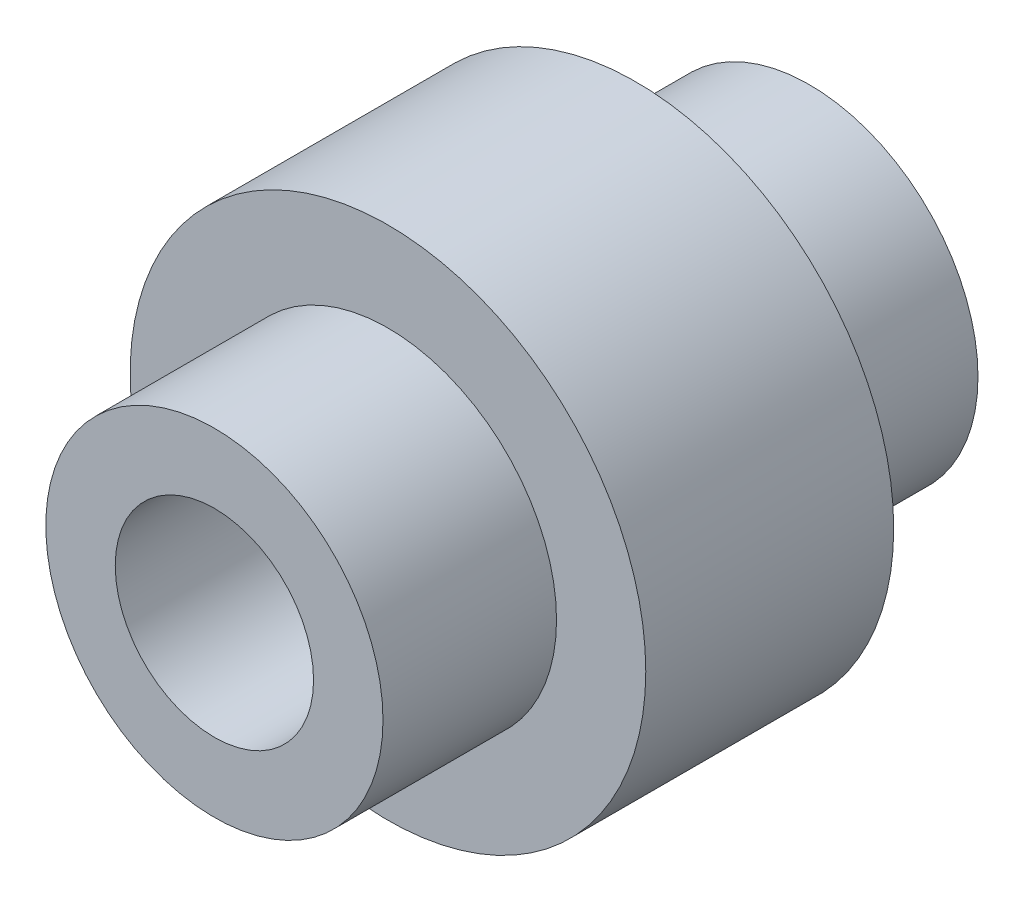
SolidWorks part; units mm, degrees
ref_plane "前视基准面" through (0, 0, 0) normal (0, 0, 1) x (1, 0, 0)
ref_plane "上视基准面" through (0, 0, 0) normal (0, 1, 0) x (1, 0, 0)
ref_plane "右视基准面" through (0, 0, 0) normal (1, 0, 0) x (0, 0, -1)
sketch "草图1" plane through (0, 0, 0) normal (0, 0, 1) x (1, 0, 0)
  line L0 (-87.1056, 0) -> (87.1056, 0) construction
  line L1 (0, 87.1056) -> (0, -87.1056) construction
  circle A0 centre (0, 0) radius 20
  circle A1 centre (0, 0) radius 34
  circle A2 centre (0, 0) radius 52
  dimension "D1" = 40
  dimension "D2" = 68
  dimension "D3" = 104
extrude "凸台-拉伸1" add sketch "草图1" along normal mid plane 50 contours A2 A1 region at (-50.5292, 0, 0)
extrude "凸台-拉伸2" add sketch "草图1<3>" along normal mid plane 120 contours A1 A0 region at (-33.0383, 0, 0)
sketch "草图1<3>" plane through (0, 0, 0) normal (0, 0, 1) x (1, 0, 0) same geometry as "草图1"
sketch "草图2" plane through (0, 0, -60) normal (0, 0, -1) x (-1, 0, 0)
  circle A0 centre (0, 0) radius 11
  circle A1 centre (0, 0) radius 20
  circle A2 centre (0, 0) radius 20 construction
  dimension "D1" = 22
extrude "凸台-拉伸3" add sketch "草图2" against normal blind 35
